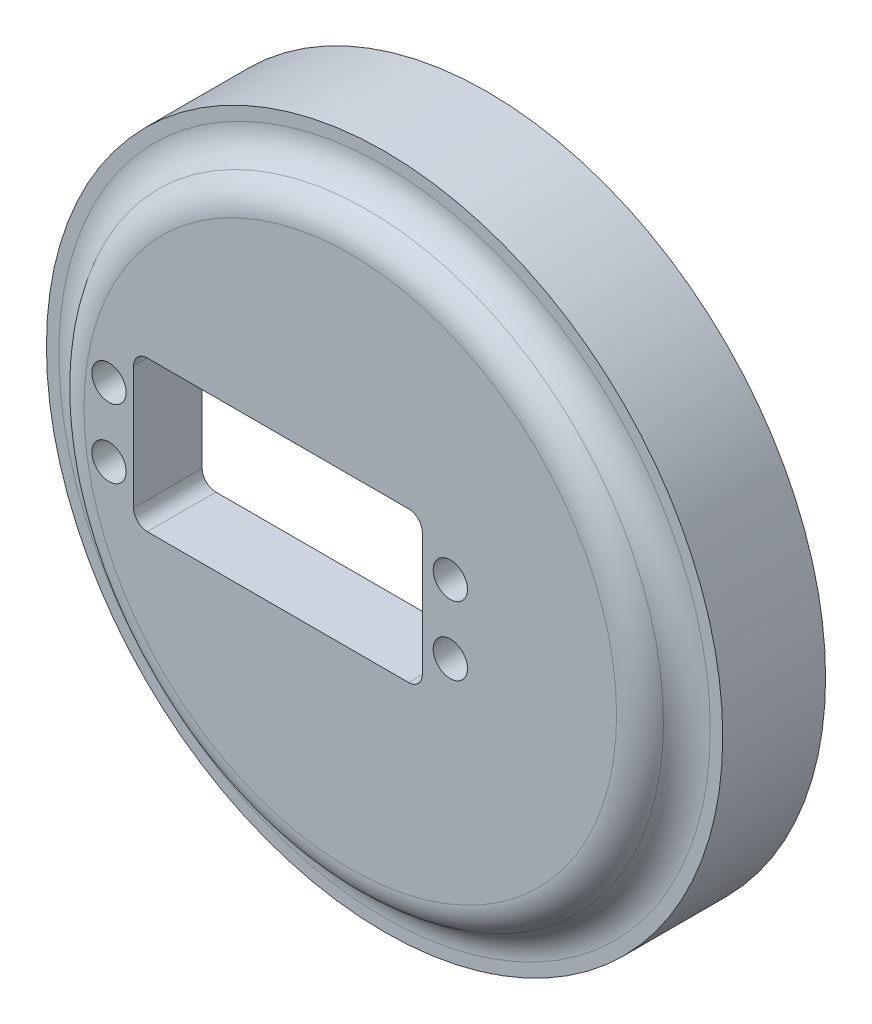
SolidWorks part; units mm, degrees
ref_plane "Front Plane" through (0, 0, 0) normal (0, 0, 1) x (1, 0, 0)
ref_plane "Top Plane" through (0, 0, 0) normal (0, 1, 0) x (1, 0, 0)
ref_plane "Right Plane" through (0, 0, 0) normal (1, 0, 0) x (0, 0, -1)
sketch "Sketch1" plane through (0, 0, 0) normal (0, 0, 1) x (1, 0, 0)
  circle A0 centre (0, 0) radius 46.32
  dimension "D1" = 92.64
extrude "Extrude-Thin1" add sketch "Sketch1" along normal blind 10 thin thin type one direction wall 3
sketch "Sketch2" plane through (0, 0, 10) normal (0, 0, 1) x (1, 0, 0)
  circle A1 centre (0, 0) radius 49.32
extrude "Boss-Extrude1" add sketch "Sketch2" along normal blind 5
sketch "Sketch3" plane through (0, 0, 15) normal (0, 0, 1) x (1, 0, 0)
  circle A0 centre (0, 0) radius 42.5
  dimension "D1" = 85
extrude "Boss-Extrude2" add sketch "Sketch3" along normal blind 5
fillet "Fillet1" radius 5 2 edges at (42.5, 0, 15) (46.32, 0, 10)
fillet "Fillet2" radius 5 1 edges at (42.5, 0, 20)
sketch "Sketch4" plane through (0, 0, 20) normal (0, 0, 1) x (1, 0, 0)
  line L1 (-31.6, 10.9) -> (10.5, 10.9)
  line L2 (-31.6, 10.9) -> (-31.6, -11.0348)
  line L3 (-31.6, -11.0348) -> (10.5, -11.0348)
  line L4 (10.5, 10.9) -> (10.5, -11.0348)
  line L5 (-31.6, 10.9) -> (10.5, -11.0348) construction
  line L6 (-31.6, -11.0348) -> (10.5, 10.9) construction
  circle A0 centre (-35.1896, 5) radius 2.5
  circle A1 centre (-35.1896, -5) radius 2.5
  circle A2 centre (14.5896, 5) radius 2.5
  circle A3 centre (14.5896, -5) radius 2.5
  circle A4 centre (0, 0) radius 38.8397 construction
  point P0 (-10.55, -0.0674)
  dimension "D1" = 49.7792
  dimension "D3" = 10
  dimension "D6" = 5
  dimension "D7" = 5
  dimension "D8" = 5
  dimension "D9" = 5
  dimension "D2" = 10.9
  dimension "D4" = 11.0348
  dimension "D5" = 42.1
extrude "Cut-Extrude1" cut sketch "Sketch4" against normal through all
fillet "Fillet3" radius 2 4 edges at (10.5, 10.9, 15) (10.5, -11.0348, 15) (-31.6, -11.0348, 15) (-31.6, 10.9, 15)
